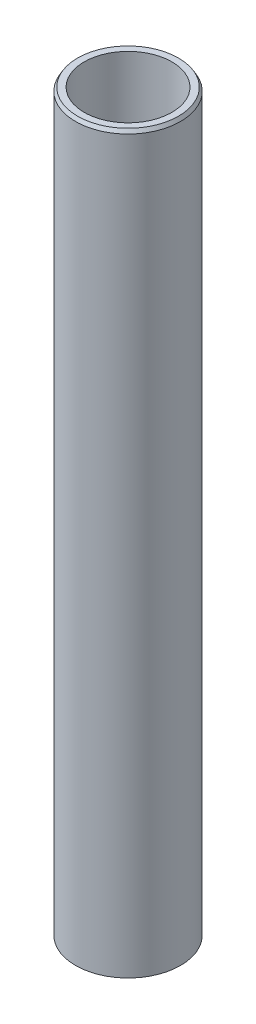
SolidWorks part; units mm, degrees
ref_plane "Front Plane" through (0, 0, 0) normal (0, 0, 1) x (1, 0, 0)
ref_plane "Top Plane" through (0, 0, 0) normal (0, 1, 0) x (1, 0, 0)
ref_plane "Right Plane" through (0, 0, 0) normal (1, 0, 0) x (0, 0, -1)
sketch "Sketch1" plane through (0, 0, 0) normal (0, 1, 0) x (1, 0, 0)
  circle A0 centre (0, 0) radius 37.5
  dimension "SHAFT_OD" = 75
extrude "Boss-Extrude1" add sketch "Sketch1" along normal blind 526.1835
sketch "Sketch2" plane through (0, 0, 0) normal (0, 1, 0) x (1, 0, 0)
  circle A0 centre (0, 0) radius 31.3052
  dimension "BORE_D" = 62.6104
extrude "Cut-Extrude1" cut sketch "Sketch2" along normal through all
chamfer "Chamfer1" distance 2.5432 angle 30 2 edges at (0, 526.1835, 37.5) (0, 0, 37.5) first distance on face at (0, 526.1835, 37.5) first distance on face at (0, 0, 31.3052)
